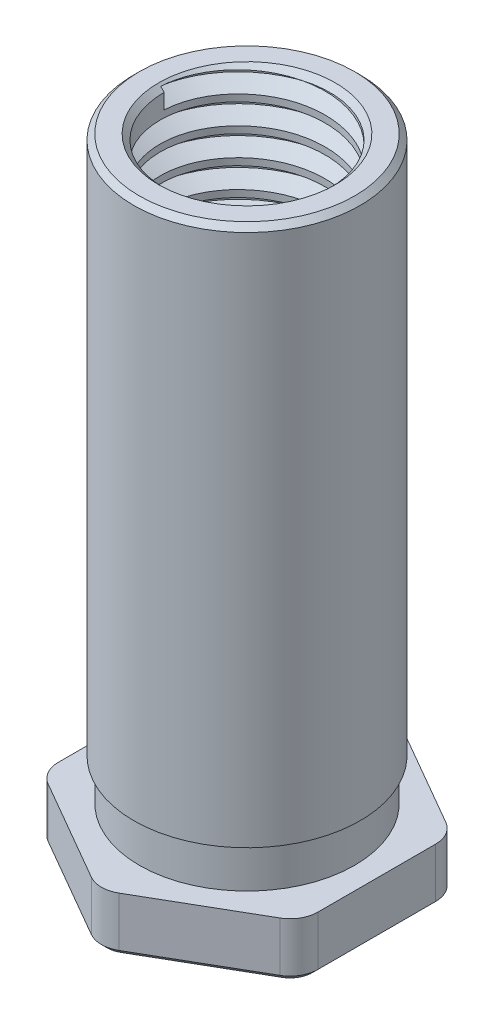
SolidWorks part; units mm, degrees
ref_plane "Front Plane" through (0, 0, 0) normal (0, 0, 1) x (1, 0, 0)
ref_plane "Top Plane" through (0, 0, 0) normal (0, 1, 0) x (1, 0, 0)
ref_plane "Right Plane" through (0, 0, 0) normal (1, 0, 0) x (0, 0, -1)
sketch "Sketch1" plane through (0, 0, 0) normal (0, 1, 0) x (1, 0, 0)
  line L1 (0, -2.7135) -> (2.35, -1.3568)
  line L2 (2.35, -1.3568) -> (2.35, 1.3568)
  line L3 (2.35, 1.3568) -> (0, 2.7135)
  line L4 (0, 2.7135) -> (-2.35, 1.3568)
  line L5 (-2.35, 1.3568) -> (-2.35, -1.3568)
  line L6 (-2.35, -1.3568) -> (0, -2.7135)
  circle A0 centre (0, 0) radius 2.35 construction
  circle A1 centre (0, 0) radius 2.05
  circle A3 centre (0, 0) radius 1.95
  dimension "D2" = 4.1
  dimension "D3" = 3.9
  dimension "D1" = 4.7
extrude "extrude hex" add sketch "Sketch1" against normal blind 1 contours A3 | A1 A3 | L5 L6 L1 L2 L3 L4 A1 region at (-1.1391, 0, 1.973) region at (-1.992, 0, 0) region at (0, 0, 0)
extrude "extrude cylinder" add sketch "Sketch1<3>" along normal blind 10.5 contours A1 | A3 region at (-1.992, 0, 0) region at (0, 0, 0)
sketch "Sketch1<3>" plane through (0, 0, 0) normal (0, 1, 0) x (1, 0, 0) same geometry as "Sketch1"
extrude "cut clincher" cut sketch "Sketch1<4>" along normal blind 0.75 contours A1 A3 region at (-1.992, 0, 0)
sketch "Sketch1<4>" plane through (0, 0, 0) normal (0, 1, 0) x (1, 0, 0) same geometry as "Sketch1"
hole_wizard "drill 3mm" positions "Sketch2" profile "Sketch3" hole size "Ø1.0" standard "ANSI Metric"
sketch "Sketch2" plane through (0, 10.5, 0) normal (0, 1, 0) x (1, 0, 0)
  point P0 (0, 0)
sketch "Sketch3" plane through (0, 10.5, 0) normal (1, 0, 0) x (0, 0, 1)
  line L0 (0, 0) -> (0, 10)
  line L1 (0, 10) -> (1.5, 10)
  line L2 (1.5, 10) -> (1.5, 0)
  line L5 (1.5, 0) -> (0, 0)
  line L10 (0, 10) -> (-1.5, 10) construction
  line L11 (0, -6.35) -> (0, 107.95) construction
  dimension "Hole Dia." = 3
  dimension "Hole Depth" = 10
  dimension "Drill Angle" = 180
thread "thread m3" pitch 0.5 method cut profile "Thread Profile1" start angle 0, offset 0, length 10, pitch 0.5, diameter 3
ref_plane "Plane1" through (-1.5, 10.5, 0) normal (0, 0, 1) x (-1, 0, 0)
sketch "Thread Profile1" plane through (-1.5, 10.5, 0) normal (0, 0, 1) x (-1, 0, 0)
  line L0 (0, 0) -> (0, 0.5) construction
  line L1 (0, 0) -> (0.2706, 0.1562)
  line L2 (0.2706, 0.1562) -> (0.2706, 0.2187)
  line L3 (0.2706, 0.2187) -> (0, 0.375)
  line L4 (0.2706, 0.1875) -> (0, 0.1875) construction
  line L11 (0, 0) -> (0, 0.375)
  point P2 (0, 0)
  dimension "Pitch" = 0.5
  dimension "Profile_Angle" = 60
  dimension "Profile_Land" = 0.0625
  dimension "Profile_Height" = 0.2706
fillet "fillet hex" radius 0.5 6 edges at (-2.35, -0.5, -1.3568) (0, -0.5, -2.7135) (2.35, -0.5, -1.3568) (2.35, -0.5, 1.3568) (0, -0.5, 2.7135) (-2.35, -0.5, 1.3568)
chamfer "chamfer visual" distance 0.1 angle 45 14 edges at (0, 10.5, 2.05) (0, 10.5, 1.5) (-2.283, -1, 1.3181) (-1.175, -1, 2.0352) (0, -1, 2.6362) (1.175, -1, 2.0352) (2.283, -1, 1.3181) (2.35, -1, 0) (2.283, -1, -1.3181) (1.175, -1, -2.0352) (0, -1, -2.6362) (-1.175, -1, -2.0352) (-2.283, -1, -1.3181) (-2.35, -1, 0)
